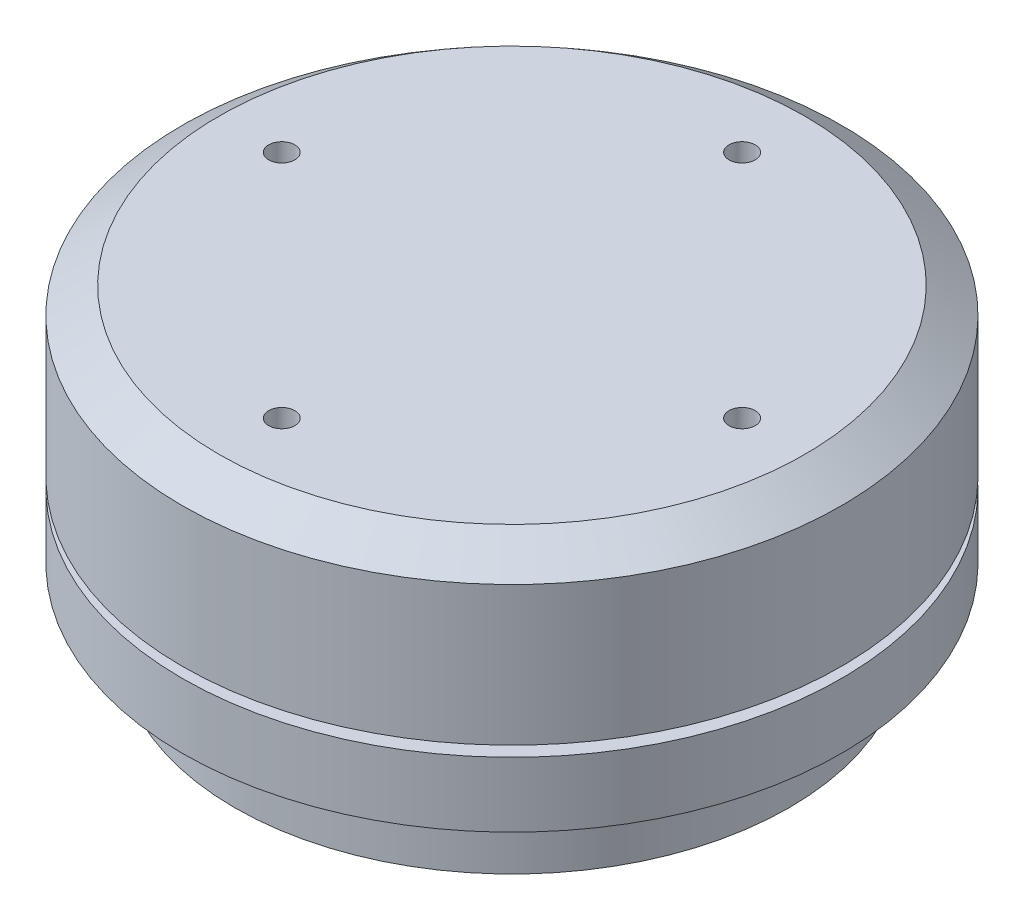
SolidWorks part; units mm, degrees
ref_plane "Спереди" through (0, 0, 0) normal (0, 0, 1) x (1, 0, 0)
ref_plane "Сверху" through (0, 0, 0) normal (0, 1, 0) x (1, 0, 0)
ref_plane "Справа" through (0, 0, 0) normal (1, 0, 0) x (0, 0, -1)
ref_axis "Axis1" through (0, 0, 0) along (0, 1, 0)
sketch "Sketch1" plane through (0, 0, 0) normal (0, 0, 1) x (1, 0, 0)
  line L0 (0, 0) -> (0, -78619.6517) construction
  line L1 (0, 0) -> (0, 30)
  line L2 (0, 30) -> (-28, 30)
  line L3 (-28, 30) -> (-31.5, 27.5)
  line L4 (-31.5, 27.5) -> (-31.5, 14.2)
  line L5 (-31.5, 14.2) -> (-29.5, 14.2)
  line L6 (-29.5, 14.2) -> (-29.5, 13.2)
  line L7 (-29.5, 13.2) -> (-31.5, 13.2)
  line L8 (-31.5, 13.2) -> (-31.5, 7)
  line L9 (-31.5, 7) -> (-26.5, 5.6)
  line L10 (-26.5, 5.6) -> (-26.5, 0)
  line L11 (-26.5, 0) -> (0, 0)
  dimension "D1" = 56
  dimension "D2" = 63
  dimension "D3" = 2.5
  dimension "D4" = 1.4
  dimension "D5" = 53
  dimension "D6" = 1
  dimension "D7" = 2
  dimension "D8" = 30
  dimension "D9" = 6.2
  dimension "D10" = 5.6
revolve "Revolve1" add sketch "Sketch1" angle 360 about L0
hole_wizard "M3x0.5 Tapped Hole1" positions "Sketch2" profile "Sketch3" tap size "M3x0.5" standard "ANSI Metric"
sketch "Sketch2" plane through (0, 30, 0) normal (0, 1, 0) x (1, 0, 0)
  circle A0 centre (0, 0) radius 22 construction
  point P0 (0, 22)
  point P39 (0, -22)
  point P44 (22, 0)
  point P69 (-22, 0)
sketch "Sketch3" plane through (0, 30, -22) normal (1, 0, 0) x (0, 0, 1)
  line L0 (0, 0) -> (0, 6.7511)
  line L1 (0, 6.7511) -> (1.25, 6)
  line L2 (1.25, 6) -> (1.25, 0)
  line L5 (1.25, 0) -> (0, 0)
  line L10 (0, 6.7511) -> (-1.25, 6) construction
  line L11 (0, -6.35) -> (0, 107.95) construction
  dimension "Tap Drill Dia." = 2.5
  dimension "Tap Drill Depth" = 6
  dimension "Drill Angle" = 118
cosmetic thread "Hole Thread1" parameters "D1"=6, "D2"=3
cosmetic thread "Hole Thread2" parameters "D1"=6, "D2"=3
cosmetic thread "Hole Thread3" parameters "D1"=6, "D2"=3
cosmetic thread "Hole Thread5" parameters "D1"=6, "D2"=3
hole_wizard "M3x0.5 Tapped Hole2" positions "Sketch4" profile "Sketch5" tap size "M3x0.5" standard "ANSI Metric"
sketch "Sketch4" plane through (0, 0, 0) normal (0, -1, 0) x (-1, 0, 0)
  circle A0 centre (0, 0) radius 15 construction
  point P2 (0, 15)
  point P40 (0, -15)
  point P45 (15, 0)
  point P54 (-15, 0)
  dimension "D1" = 30
sketch "Sketch5" plane through (0, 0, -15) normal (1, 0, 0) x (0, 0, -1)
  line L0 (0, 0) -> (0, 9.2511)
  line L1 (0, 9.2511) -> (1.25, 8.5)
  line L2 (1.25, 8.5) -> (1.25, 0)
  line L5 (1.25, 0) -> (0, 0)
  line L10 (0, 9.2511) -> (-1.25, 8.5) construction
  line L11 (0, -6.35) -> (0, 107.95) construction
  dimension "Tap Drill Dia." = 2.5
  dimension "Tap Drill Depth" = 8.5
  dimension "Drill Angle" = 118
cosmetic thread "Hole Thread8" parameters "D1"=6, "D2"=3
cosmetic thread "Hole Thread9" parameters "D1"=6, "D2"=3
cosmetic thread "Hole Thread11" parameters "D1"=6, "D2"=3
cosmetic thread "Hole Thread13" parameters "D1"=6, "D2"=3
